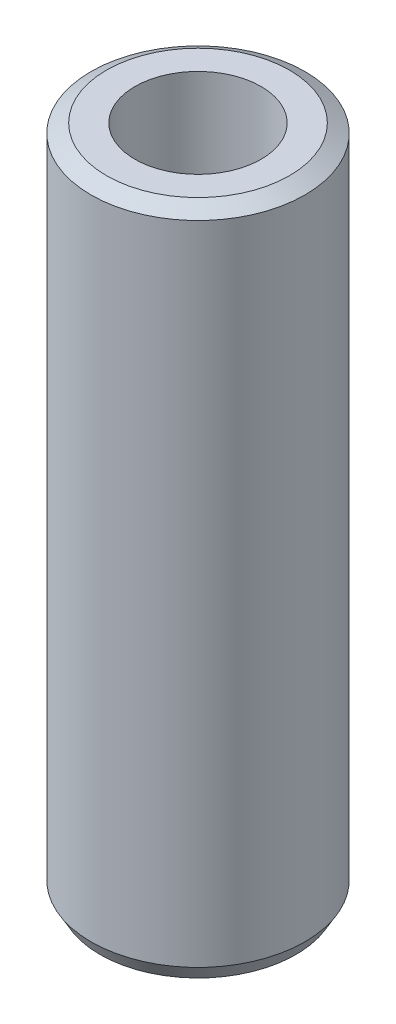
SolidWorks part; units mm, degrees
ref_plane "Front Plane" through (0, 0, 0) normal (0, 0, 1) x (1, 0, 0)
ref_plane "Top Plane" through (0, 0, 0) normal (0, 1, 0) x (1, 0, 0)
ref_plane "Right Plane" through (0, 0, 0) normal (1, 0, 0) x (0, 0, -1)
sketch "Sketch1" plane through (0, 0, 0) normal (0, 1, 0) x (1, 0, 0)
  circle A0 centre (0, 0) radius 60
  dimension "SHAFT_OD" = 120
extrude "Boss-Extrude1" add sketch "Sketch1" along normal blind 376.55
sketch "Sketch2" plane through (0, 0, 0) normal (0, 1, 0) x (1, 0, 0)
  circle A0 centre (0, 0) radius 35.3905
  dimension "BORE_D" = 70.7811
extrude "Cut-Extrude1" cut sketch "Sketch2" along normal through all
chamfer "Chamfer1" distance 5.0134 angle 60 2 edges at (0, 376.55, 60) (0, 0, 60) first distance on face at (0, 376.55, 60) first distance on face at (0, 0, 35.3905)
